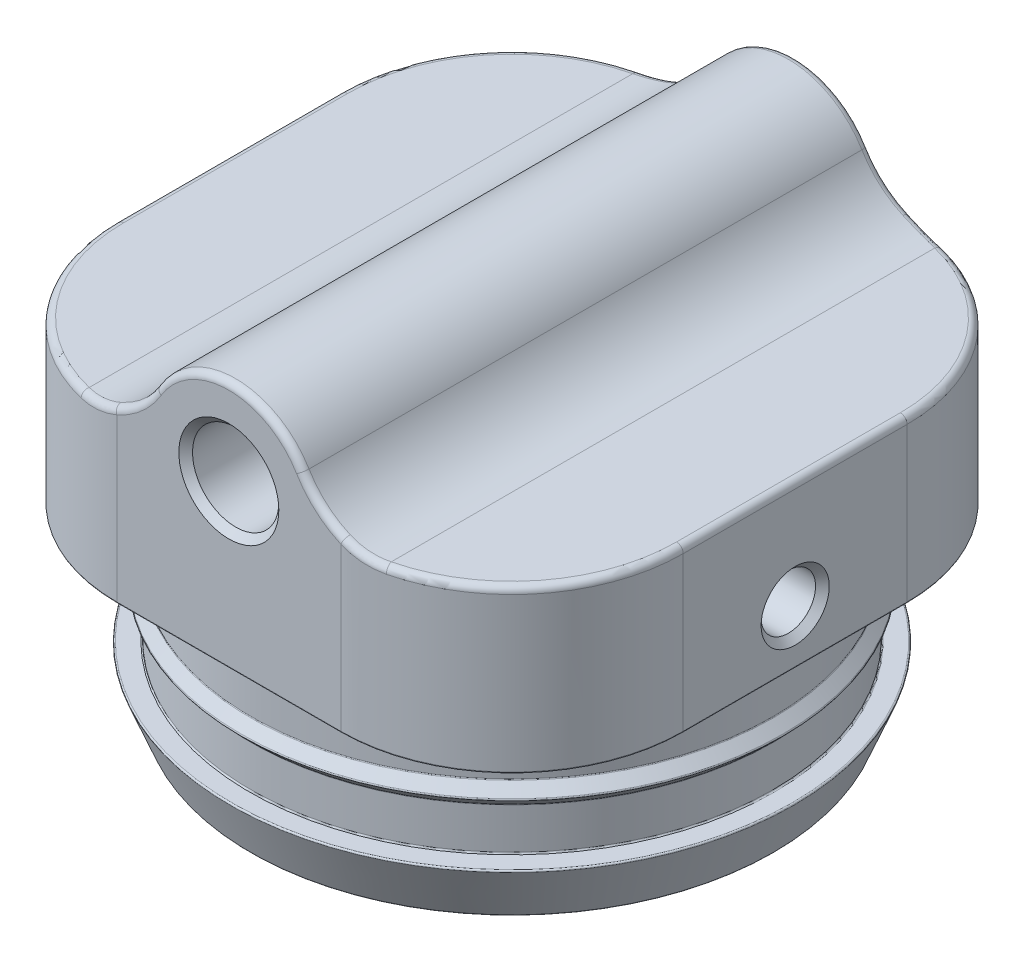
SolidWorks part; units mm, degrees
ref_plane "Front Plane" through (0, 0, 0) normal (0, 0, 1) x (1, 0, 0)
ref_plane "Top Plane" through (0, 0, 0) normal (0, 1, 0) x (1, 0, 0)
ref_plane "Right Plane" through (0, 0, 0) normal (1, 0, 0) x (0, 0, -1)
sketch "Sketch1" plane through (0, 0, 0) normal (0, 0, 1) x (1, 0, 0)
  line L3 (0, 0) -> (0, -12) construction
  line L4 (-21, 0) -> (-6.35, 0)
  line L5 (-21, 0) -> (-21, -12)
  line L6 (-21, -12) -> (21, -12)
  line L7 (21, 0) -> (21, -12)
  line L8 (6.35, 0) -> (21, 0)
  circle A0 centre (0, 0) radius 3.2
  arc A1 (6.35, 0) -> (-6.35, 0) centre (0, 0) ccw
  dimension "D1" = 6.4
  dimension "D2" = 12.7
  dimension "D4" = 42
  dimension "D5" = 12
extrude "Boss-Extrude1" add sketch "Sketch1" along normal mid plane 42
sketch3d "3DSketch1" plane through (0, 0, 0) normal (0, 0, 1) x (1, 0, 0)
  dimension "D1" = 12.7
sketch "Sketch2" plane through (0, 0, 0) normal (0, 0, 1) x (1, 0, 0)
  line L0 (0, 9.544) -> (0, -9.544) construction
  line L1 (0, -12) -> (19.365, -12)
  line L2 (-21, -12) -> (21, -12) construction
  line L4 (0, -24.7) -> (19.365, -24.7)
  line L10 (0, -24.7) -> (0, -12)
  line L11 (19.365, -24.7) -> (20.9525, -20.7312)
  line L12 (20.9525, -20.7312) -> (19.365, -20.7312)
  line L13 (19.365, -20.7312) -> (19.365, -17.5562)
  line L14 (19.365, -17.5562) -> (20.1588, -16.7625)
  line L15 (20.1588, -16.7625) -> (19.365, -15.9687)
  line L16 (20.1588, -16.7625) -> (19.365, -16.7625) construction
  line L17 (19.365, -15.9687) -> (19.365, -12)
  dimension "D1" = 38.73
  dimension "D2" = 12.7
  dimension "D3" = 1.5875
  dimension "D4" = 8.7312
  dimension "D5" = 0.7937
  dimension "D6" = 7.9375
revolve "Revolve1" add sketch "Sketch2" angle 360 about L0
sketch "Sketch3" plane through (0, -24.7, 0) normal (0, -1, 0) x (1, 0, 0)
  circle A0 centre (0, 0) radius 4
  dimension "D1" = 8
extrude "Cut-Extrude1" cut sketch "Sketch3" against normal blind 6.5 and the other way through all from surface contours A0 starting at face at (-19.365, -12, 0)
hole_wizard "#10-32 Tapped Hole1" positions "Sketch4" profile "Sketch5" tap size "#10-32" standard "ANSI Inch" end condition up to next
sketch "Sketch4" plane through (21, 0, 0) normal (1, 0, 0) x (0, 0, -1)
  line L0 (-21, -12) -> (21, -12) construction
  point P0 (0, -8)
  dimension "D1" = 4
cosmetic thread "Hole Thread1" parameters "D2"=4.826
sketch "Sketch5" plane through (21, -8, 0) normal (0, 1, 0) x (0, 0, -1)
  line L0 (0, 0) -> (0, 17)
  line L1 (0, 17) -> (2.0193, 17)
  line L2 (2.0193, 17) -> (2.0193, 0)
  line L5 (2.0193, 0) -> (0, 0)
  line L11 (0, -6.35) -> (0, 107.95) construction
  dimension "Thru Tap Drill Dia." = 4.0386
  dimension "Thru Tap Drill Depth" = 17
sketch "Sketch6" [suppressed] plane through (0, 0, 0) normal (1, 0, 0) x (0, 0, -1)
  line L0 (0, -1000) -> (0, 49000) construction
  line L1 (-21, -12) -> (-21, 0) construction
  line L2 (-21, -5.65) -> (-12.7, -5.65)
  line L3 (-21, -5.65) -> (-21, 6.35)
  line L4 (-21, 6.35) -> (-12.7, 6.35)
  line L5 (-12.7, -5.65) -> (-12.7, 6.35)
  line L6 (21, 6.35) -> (-21, 6.35) construction
  line L7 (-21, -12) -> (21, -12) construction
  line L8 (12.7, -5.65) -> (12.7, 6.35)
  line L9 (21, 6.35) -> (12.7, 6.35)
  line L10 (21, -5.65) -> (21, 6.35)
  line L11 (21, -5.65) -> (12.7, -5.65)
  dimension "D1" = 12.7
  dimension "D2" = 6.35
extrude "Cut-Extrude2" [suppressed] cut sketch "Sketch6" against normal mid plane 42
fillet "Fillet3" radius 0.1 12 edges at (-20.9525, -20.7313, 0) (-20.1587, -16.7625, 0) (-4, -5.5, 0) (-19.365, -24.7, 0) (-19.365, -12, 0) (-19.365, -15.9687, 0) (-19.365, -17.5562, 0) (-19.365, -20.7313, 0) (-21, -12, 0) (0, -12, 21) (21, -12, 0) (0, -12, -21)
chamfer "Chamfer1" distance 0.508 angle 45 4 edges at (3.2, 0, -21) (3.2, 0, 21) (21, -8, -2.0193) (-4, -24.7, 0)
fillet "Fillet7" radius 6.7 2 edges at (-6.35, 0, 0) (6.35, 0, 0)
fillet "Fillet6" radius 12.7 8 edges at (21, -5.95, -21) (-21, -5.95, -21) (-21, -5.95, 21) (21, -5.95, 21) (20.9707, -11.9707, 20.9707) (-20.9707, -11.9707, 20.9707) (-20.9707, -11.9707, -20.9707) (20.9707, -11.9707, -20.9707)
fillet "Fillet8" radius 0.5 16 edges at (18.2525, 0, 16.1891) (10.2375, 0.0693, 20.8513) (6.6833, 1.7502, 21) (0, 6.35, 21) (-6.6833, 1.7502, 21) (-9.2132, 0.301, 20.9671) (-18.2525, 0, 16.1891) (-21, 0, 0) (-18.2525, 0, -16.1891) (-10.2375, 0.0693, -20.8513) (-6.6833, 1.7502, -21) (0, 6.35, -21) (6.6833, 1.7502, -21) (9.2132, 0.301, -20.9671) (18.2525, 0, -16.1891) (21, 0, 0)
fillet "Fillet9" radius 3.5 1 edges at (3.4594, -8.2115, 2.0082)
